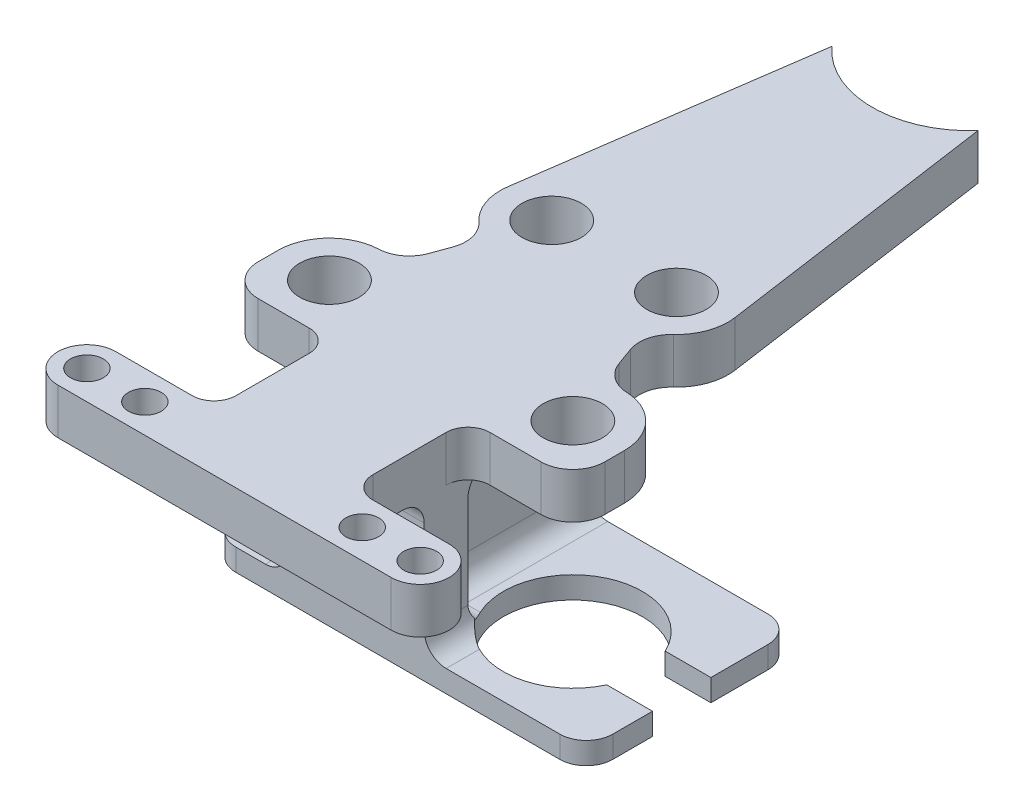
SolidWorks part; units mm, degrees
ref_plane "Front Plane" through (0, 0, 0) normal (0, 0, 1) x (1, 0, 0)
ref_plane "Top Plane" through (0, 0, 0) normal (0, 1, 0) x (1, 0, 0)
ref_plane "Right Plane" through (0, 0, 0) normal (1, 0, 0) x (0, 0, -1)
sketch "Sketch1" plane through (0, 0, 0) normal (0, 1, 0) x (1, 0, 0)
  line L0 (0, 39.5936) -> (0, -19.0103) construction
  line L7 (6.8366, 23.5042) -> (13.335, 5.65) construction
  line L14 (10.4435, 13.5943) -> (9.7281, 15.5599)
  line L21 (6.8366, 29.1542) -> (-6.8366, 29.1542) construction
  line L23 (-10.4435, 13.5943) -> (-9.7281, 15.5599)
  line L24 (18.985, 5.65) -> (18.985, 3.5)
  line L26 (15.485, 0) -> (-15.485, 0)
  line L27 (-18.985, 5.65) -> (-18.985, 3.5)
  line L28 (-8, 55.375) -> (-12.4301, 24.3016)
  line L29 (8, 55.375) -> (12.4301, 24.3016)
  line L30 (13.335, 2.4) -> (13.335, 0) construction
  circle A31 centre (6.8366, 23.5042) radius 3.25
  circle A32 centre (13.335, 5.65) radius 3.25
  arc A33 (18.985, 5.65) -> (13.5804, 11.2947) centre (13.335, 5.65) ccw
  arc A34 (13.5804, 11.2947) -> (10.4435, 13.5943) centre (13.7324, 14.7914) cw
  arc A35 (9.7281, 15.5599) -> (10.6529, 19.3378) centre (13.017, 16.7569) cw
  arc A36 (10.6529, 19.3378) -> (12.4301, 24.3016) centre (6.8366, 23.5042) ccw
  circle A37 centre (-13.335, 5.65) radius 3.25
  circle A38 centre (-6.8366, 23.5042) radius 3.25
  arc A39 (-10.6529, 19.3378) -> (-12.4301, 24.3016) centre (-6.8366, 23.5042) cw
  arc A40 (-9.7281, 15.5599) -> (-10.6529, 19.3378) centre (-13.017, 16.7569) ccw
  arc A41 (-13.5804, 11.2947) -> (-10.4435, 13.5943) centre (-13.7324, 14.7914) ccw
  arc A42 (-18.985, 5.65) -> (-13.5804, 11.2947) centre (-13.335, 5.65) cw
  arc A43 (18.985, 3.5) -> (15.485, 0) centre (15.485, 3.5) cw
  arc A44 (-18.985, 3.5) -> (-15.485, 0) centre (-15.485, 3.5) ccw
  circle A45 centre (0, 62.5042) radius 10.7156 construction
  arc A46 (-8, 55.375) -> (8, 55.375) centre (0, 62.5042) ccw
  point P31 (0, 29.1542)
  point P38 (0, 0)
  point P41 (0, 0)
  dimension "D7" = 3.5
  dimension "D8" = 3.5
  dimension "D2" = 19
  dimension "D6" = 13.335
  dimension "D9" = 2.4
  dimension "D11" = 21.4312
  dimension "D12" = 16
  dimension "D10" = 33.35
  dimension "D3" = 6.5
  dimension "D4" = 2.4
  dimension "D5" = 2.4
  dimension "D1" = 20
  dimension "D13" = 13.6732
extrude "Boss-Extrude1" add sketch "Sketch1" along normal blind 5
ref_plane "Plane1" through (0, -15, 0) normal (0, -1, 0) x (-1, 0, 0)
sketch "Sketch3" plane through (0, -15, 0) normal (0, -1, 0) x (-1, 0, 0)
  line L0 (-25.26, 8.85) -> (-20.2505, 8.85)
  line L1 (0, 0) -> (0, 7.062) construction
  line L2 (15.485, 0) -> (-15.485, 0) construction
  line L3 (13.14, -4.8) -> (-22.36, -4.8)
  line L8 (-13.335, 5.65) -> (-25.26, 5.65) construction
  line L12 (7.22, 18) -> (-13.335, 18)
  line L13 (16.04, -1.9) -> (16.04, 9.18)
  line L15 (-13.335, -1.97) -> (-13.335, -4.8) construction
  line L16 (-25.26, 2.45) -> (-20.2505, 2.45)
  line L17 (-25.26, 2.45) -> (-25.26, 8.85)
  line L18 (-22.36, 18) -> (-13.335, 18)
  line L19 (-25.26, -1.9) -> (-25.26, 2.45)
  line L20 (-25.26, 15.1) -> (-25.26, 8.85)
  circle A0 centre (-13.335, 5.65) radius 3.25 construction
  circle A1 centre (-13.335, 5.65) radius 3.25 construction
  circle A3 centre (13.14, 5.65) radius 1.7
  arc A4 (-20.2505, 2.45) -> (-20.2505, 8.85) centre (-13.335, 5.65) ccw
  arc A9 (-22.36, -4.8) -> (-25.26, -1.9) centre (-22.36, -1.9) cw
  arc A10 (-25.26, 15.1) -> (-22.36, 18) centre (-22.36, 15.1) cw
  arc A11 (13.14, 12.08) -> (16.04, 9.18) centre (13.14, 9.18) cw
  arc A15 (13.14, 12.08) -> (10.18, 15.04) centre (13.14, 15.04) cw
  arc A16 (10.18, 15.04) -> (7.22, 18) centre (7.22, 15.04) ccw
  arc A18 (13.14, -4.8) -> (16.04, -1.9) centre (13.14, -1.9) ccw
  point P23 (0, 0)
  dimension "D3" = 2.9
  dimension "D7" = 5.0095
  dimension "D6" = 3.4
  dimension "D12" = 2.83
  dimension "D4" = 7.62
  dimension "D8" = 2.96
  dimension "D2" = 6.4
  dimension "D5" = 35.5
  dimension "D9" = 22.8
  dimension "D10" = 3.53
extrude "Boss-Extrude2" add sketch "Sketch3" along normal blind 2.4 separate body contours L3 A18 L13 A11 A15 A16 L12 L18 A10 L20 L0 A4 L16 L19 A9 A3 region at (2.62, -15, -6.4804)
sketch "Sketch4" plane through (0, -17.4, 0) normal (0, -1, 0) x (1, 0, 0)
  line L0 (-15.485, 0) -> (15.485, 0) construction
  line L1 (-15.485, 0) -> (15.485, 0) construction
  line L4 (0, 0) -> (0, -25.8726) construction
  line L5 (-2.4, 0) -> (-2.4, -18)
  line L6 (-2.4, -18) -> (2.4, -18)
  line L7 (2.4, -18) -> (2.4, 0)
  line L8 (2.4, 0) -> (7.5, 0)
  line L9 (7.5, 0) -> (7.5, 4.8)
  line L10 (7.5, 4.8) -> (-7.5, 4.8)
  line L11 (-7.5, 4.8) -> (-7.5, 0)
  line L12 (-7.5, 0) -> (-2.4, 0)
  dimension "D1" = 18
  dimension "D2" = 4.8
  dimension "D3" = 4.8
  dimension "D4" = 15
extrude "Boss-Extrude3" add sketch "Sketch4" against normal up to surface (22.4 mm away) up to face at (0, 5, -16.2916)
sketch "Sketch5" plane through (0, 5, 0) normal (0, 1, 0) x (1, 0, 0)
  line L0 (7.5, -12.825) -> (18.2562, -12.825)
  line L1 (18.2562, -19.175) -> (-18.2562, -19.175)
  line L2 (-18.2562, -12.825) -> (-7.5, -12.825)
  line L3 (-7.5, -4.8) -> (7.5, -4.8)
  line L5 (7.5, -12.825) -> (7.5, -4.8)
  line L6 (-7.5, -12.825) -> (-7.5, -4.8)
  line L7 (0, -4.8) -> (0, -8.0211) construction
  line L8 (-7.5, -4.8) -> (7.5, -4.8) construction
  circle A4 centre (18.2562, -16) radius 1.8
  circle A5 centre (11.9062, -16) radius 1.8
  circle A6 centre (-11.9062, -16) radius 1.8
  circle A7 centre (-18.2562, -16) radius 1.8
  arc A8 (18.2562, -12.825) -> (18.2562, -19.175) centre (18.2562, -16) cw
  arc A9 (-18.2562, -19.175) -> (-18.2562, -12.825) centre (-18.2562, -16) cw
  dimension "D1" = 6.35
  dimension "D2" = 3.6
  dimension "D3" = 6.35
  dimension "D4" = 6.35
  dimension "D5" = 23.8125
  dimension "D6" = 3.2211
  dimension "D7" = 11.2
extrude "Boss-Extrude4" add sketch "Sketch5" against normal up to surface (5 mm away) up to face at (0, 0, -13.7187)
fillet "Fillet1" radius 2.4 13 edges at (2.4, 0, -9) (-2.4, 0, -9) (-2.4, -7.5, 0) (2.4, -7.5, 0) (-7.5, 2.5, 0) (7.5, 2.5, 12.825) (7.5, 2.5, 0) (-7.5, 2.5, 12.825) (2.4, -15, -9) (-7.5, -15, 2.4) (-2.4, -15, -9) (-4.95, -15, 0) (4.95, -15, 0)
fillet "Fillet2" radius 2.4 6 edges at (3.1029, -0.7029, -0.7029) (-3.1029, -0.7029, -0.7029) (6.15, 0, 0) (-6.15, 0, 0) (0, 0, 4.8) (7.5, -15, 2.0254)
